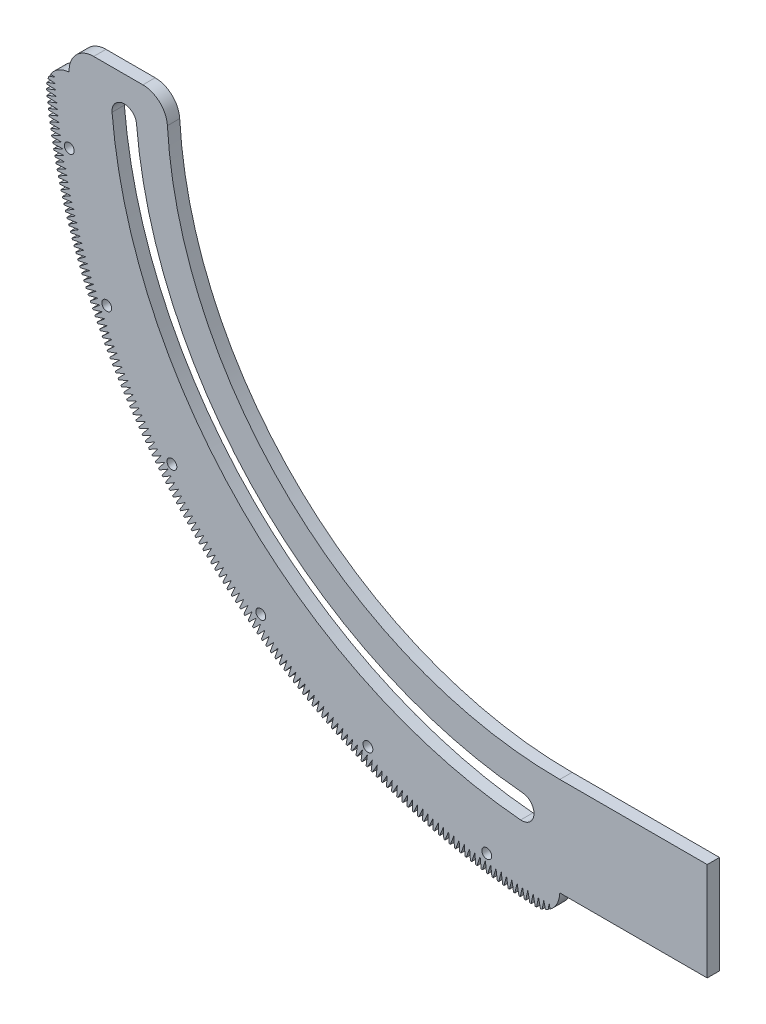
SolidWorks part; units mm, degrees
ref_plane "Front Plane" through (0, 0, 0) normal (0, 0, 1) x (1, 0, 0)
ref_plane "Top Plane" through (0, 0, 0) normal (0, 1, 0) x (1, 0, 0)
ref_plane "Right Plane" through (0, 0, 0) normal (1, 0, 0) x (0, 0, -1)
sketch "Sketch1" plane through (0, 0, 0) normal (0, 0, 1) x (1, 0, 0)
  line L0 (0, 0) -> (-203.2, 0) construction
  line L1 (0, 0) -> (0, -203.2) construction
  line L2 (0, -203.2) -> (76.2, -203.2)
  line L3 (0, -254) -> (76.2, -254)
  line L4 (-254, 0) -> (-203.2, 0)
  line L5 (76.2, -203.2) -> (76.2, -254)
  arc A0 (-203.2, 0) -> (0, -203.2) centre (0, 0) ccw
  arc A1 (-254, 0) -> (0, -254) centre (0, 0) ccw
  dimension "D1" = 50.8
  dimension "D2" = 76.2
  dimension "D3" = 203.2
extrude "Boss-Extrude1" add sketch "Sketch1" along normal blind 6.35
ref_plane "Mid_Plane" through (0, 0, 3.175) normal (0, 0, 1) x (1, 0, 0)
sketch "Sketch2" plane through (0, 0, 6.35) normal (0, 0, 1) x (1, 0, 0)
  line L0 (0, 0) -> (-229.3095, 0) construction
  line L1 (0, 0) -> (-225.1381, -19.697) construction
  line L2 (0, 0) -> (-19.697, -225.1381) construction
  arc A0 (-225.1381, -19.697) -> (-19.697, -225.1381) centre (0, 0) ccw construction
  arc A1 (-225.1381, -19.697) -> (-19.697, -225.1381) centre (0, 0) ccw construction
  arc A2 (-231.4639, -20.2505) -> (-20.2505, -231.4639) centre (0, 0) ccw
  arc A3 (-218.8123, -19.1436) -> (-19.1436, -218.8123) centre (0, 0) ccw
  arc A4 (-218.8123, -19.1436) -> (-231.4639, -20.2505) centre (-225.1381, -19.697) ccw
  arc A5 (-20.2505, -231.4639) -> (-19.1436, -218.8123) centre (-19.697, -225.1381) ccw
  point P5 (-159.8048, -159.8048)
  dimension "D1" = 80
  dimension "D3" = 12.7
  dimension "D2" = 5
extrude "Cut-Extrude1" cut sketch "Sketch2" against normal up to next
fillet "Fillet1" radius 12.7 2 edges at (-203.2, 0, 3.175) (-254, 0, 3.175)
ref_point "Mid_Point"
sketch "Sketch4" plane through (0, 0, 0) normal (0, 0, -1) x (-1, 0, 0)
  line L0 (253.648, -13.3684) -> (266.3304, -14.0368)
  line L1 (0, -254) -> (0, -266.7)
  arc A0 (0, -254) -> (253.648, -13.3684) centre (0, 0) ccw construction
  arc A1 (0, -254) -> (253.648, -13.3684) centre (0, 0) ccw
  arc A2 (0, -266.7) -> (266.3304, -14.0368) centre (0, 0) ccw
extrude "Boss-Extrude3" add sketch "Sketch4" against normal up to surface (6.35 mm away) up to face at (-139.6681, -139.6681, 6.35)
fillet "Fillet2" radius 12.7 2 edges at (-266.3304, -14.0368, 3.175) (0, -266.7, 3.175)
sketch "Sketch5" plane through (0, 0, 0) normal (0, 0, -1) x (-1, 0, 0)
  line L0 (2.758, -261.6055) -> (3.6103, -266.6756)
  line L1 (0, 0) -> (306.4939, -16.1536) construction
  line L2 (0, -261.62) -> (0.7987, -266.6988)
  line L3 (0, -261.62) -> (-1.3603, -266.6965)
  line L4 (2.758, -261.6055) -> (1.4514, -266.6961)
  line L5 (5.5157, -261.5618) -> (6.4214, -266.6227)
  line L6 (5.5157, -261.5618) -> (4.2628, -266.6659)
  line L7 (8.2728, -261.4892) -> (9.2318, -266.5402)
  line L8 (8.2728, -261.4892) -> (7.0738, -266.6062)
  line L9 (11.029, -261.3874) -> (12.0411, -266.428)
  line L10 (11.029, -261.3874) -> (9.884, -266.5168)
  line L11 (13.7839, -261.2566) -> (14.8492, -266.2863)
  line L12 (13.7839, -261.2566) -> (12.693, -266.3978)
  line L13 (16.5374, -261.0968) -> (17.6555, -266.115)
  line L14 (16.5374, -261.0968) -> (15.5007, -266.2492)
  line L15 (19.2889, -260.908) -> (20.46, -265.914)
  line L16 (19.2889, -260.908) -> (18.3067, -266.071)
  line L17 (22.0384, -260.6901) -> (23.2621, -265.6836)
  line L18 (22.0384, -260.6901) -> (21.1106, -265.8632)
  line L19 (24.7854, -260.4433) -> (26.0617, -265.4236)
  line L20 (24.7854, -260.4433) -> (23.9122, -265.6259)
  line L21 (27.5296, -260.1675) -> (28.8583, -265.1341)
  line L22 (27.5296, -260.1675) -> (26.7111, -265.359)
  line L23 (30.2708, -259.8629) -> (31.6518, -264.8151)
  line L24 (30.2708, -259.8629) -> (29.507, -265.0627)
  line L25 (33.0086, -259.5293) -> (34.4417, -264.4667)
  line L26 (33.0086, -259.5293) -> (32.2997, -264.7369)
  line L27 (35.7427, -259.1669) -> (37.2278, -264.089)
  line L28 (35.7427, -259.1669) -> (35.0888, -264.3817)
  line L29 (38.4729, -258.7757) -> (40.0098, -263.6818)
  line L30 (38.4729, -258.7757) -> (37.874, -263.9971)
  line L31 (41.1988, -258.3557) -> (42.7873, -263.2454)
  line L32 (41.1988, -258.3557) -> (40.6549, -263.5831)
  line L33 (43.9201, -257.9071) -> (45.5601, -262.7797)
  line L34 (43.9201, -257.9071) -> (43.4314, -263.1399)
  line L35 (46.6365, -257.4297) -> (48.3278, -262.2848)
  line L36 (46.6365, -257.4297) -> (46.203, -262.6674)
  line L37 (49.3478, -256.9238) -> (51.0902, -261.7607)
  line L38 (49.3478, -256.9238) -> (48.9695, -262.1657)
  line L39 (52.0535, -256.3893) -> (53.8468, -261.2076)
  line L40 (52.0535, -256.3893) -> (51.7305, -261.6349)
  line L41 (54.7535, -255.8263) -> (56.5975, -260.6254)
  line L42 (54.7535, -255.8263) -> (54.4858, -261.0751)
  line L43 (57.4474, -255.2348) -> (59.3419, -260.0143)
  line L44 (57.4474, -255.2348) -> (57.2351, -260.4862)
  line L45 (60.1349, -254.615) -> (62.0797, -259.3743)
  line L46 (60.1349, -254.615) -> (59.978, -259.8683)
  line L47 (62.8157, -253.9669) -> (64.8106, -258.7054)
  line L48 (62.8157, -253.9669) -> (62.7142, -259.2216)
  line L49 (65.4896, -253.2906) -> (67.5342, -258.0078)
  line L50 (65.4896, -253.2906) -> (65.4434, -258.546)
  line L51 (68.1561, -252.5862) -> (70.2504, -257.2815)
  line L52 (68.1561, -252.5862) -> (68.1654, -257.8418)
  line L53 (70.8151, -251.8536) -> (72.9588, -256.5266)
  line L54 (70.8151, -251.8536) -> (70.8798, -257.1088)
  line L55 (73.4663, -251.0931) -> (75.6591, -255.7432)
  line L56 (73.4663, -251.0931) -> (73.5863, -256.3473)
  line L57 (76.1092, -250.3046) -> (78.3509, -254.9314)
  line L58 (76.1092, -250.3046) -> (76.2846, -255.5573)
  line L59 (78.7437, -249.4884) -> (81.0341, -254.0913)
  line L60 (78.7437, -249.4884) -> (78.9745, -254.7389)
  line L61 (81.3695, -248.6444) -> (83.7082, -253.2229)
  line L62 (81.3695, -248.6444) -> (81.6556, -253.8922)
  line L63 (83.9862, -247.7728) -> (86.373, -252.3263)
  line L64 (83.9862, -247.7728) -> (84.3276, -253.0173)
  line L65 (86.5935, -246.8736) -> (89.0283, -251.4018)
  line L66 (86.5935, -246.8736) -> (86.9902, -252.1142)
  line L67 (89.1913, -245.947) -> (91.6736, -250.4493)
  line L68 (89.1913, -245.947) -> (89.6432, -251.1832)
  line L69 (91.7791, -244.9931) -> (94.3088, -249.4689)
  line L70 (91.7791, -244.9931) -> (92.2862, -250.2242)
  line L71 (94.3567, -244.0119) -> (96.9335, -248.4608)
  line L72 (94.3567, -244.0119) -> (94.919, -249.2374)
  line L73 (96.9239, -243.0037) -> (99.5474, -247.4252)
  line L74 (96.9239, -243.0037) -> (97.5412, -248.2229)
  line L75 (99.4803, -241.9684) -> (102.1502, -246.362)
  line L76 (99.4803, -241.9684) -> (100.1525, -247.1808)
  line L77 (102.0256, -240.9062) -> (104.7417, -245.2714)
  line L78 (102.0256, -240.9062) -> (102.7528, -246.1113)
  line L79 (104.5596, -239.8173) -> (107.3215, -244.1536)
  line L80 (104.5596, -239.8173) -> (105.3416, -245.0144)
  line L81 (107.0819, -238.7017) -> (109.8895, -243.0086)
  line L82 (107.0819, -238.7017) -> (107.9187, -243.8902)
  line L83 (109.5924, -237.5595) -> (112.4452, -241.8367)
  line L84 (109.5924, -237.5595) -> (110.4838, -242.739)
  line L85 (112.0907, -236.391) -> (114.9884, -240.6378)
  line L86 (112.0907, -236.391) -> (113.0366, -241.5608)
  line L87 (114.5765, -235.1962) -> (117.5188, -239.4122)
  line L88 (114.5765, -235.1962) -> (115.5769, -240.3557)
  line L89 (117.0496, -233.9753) -> (120.0362, -238.16)
  line L90 (117.0496, -233.9753) -> (118.1043, -239.124)
  line L91 (119.5096, -232.7283) -> (122.5402, -236.8814)
  line L92 (119.5096, -232.7283) -> (120.6186, -237.8656)
  line L93 (121.9564, -231.4555) -> (125.0306, -235.5764)
  line L94 (121.9564, -231.4555) -> (123.1195, -236.5808)
  line L95 (124.3897, -230.157) -> (127.5071, -234.2452)
  line L96 (124.3897, -230.157) -> (125.6067, -235.2697)
  line L97 (126.8091, -228.8329) -> (129.9695, -232.888)
  line L98 (126.8091, -228.8329) -> (128.0799, -233.9325)
  line L99 (129.2144, -227.4833) -> (132.4174, -231.5049)
  line L100 (129.2144, -227.4833) -> (130.539, -232.5693)
  line L101 (131.6054, -226.1085) -> (134.8505, -230.0961)
  line L102 (131.6054, -226.1085) -> (132.9835, -231.1802)
  line L103 (133.9817, -224.7085) -> (137.2687, -228.6617)
  line L104 (133.9817, -224.7085) -> (135.4132, -229.7654)
  line L105 (136.3432, -223.2836) -> (139.6717, -227.2019)
  line L106 (136.3432, -223.2836) -> (137.8279, -228.3251)
  line L107 (138.6895, -221.8339) -> (142.0591, -225.7169)
  line L108 (138.6895, -221.8339) -> (140.2272, -226.8595)
  line L109 (141.0203, -220.3595) -> (144.4307, -224.2067)
  line L110 (141.0203, -220.3595) -> (142.611, -225.3686)
  line L111 (143.3355, -218.8606) -> (146.7863, -222.6717)
  line L112 (143.3355, -218.8606) -> (144.9789, -223.8526)
  line L113 (145.6348, -217.3374) -> (149.1256, -221.1119)
  line L114 (145.6348, -217.3374) -> (147.3307, -222.3118)
  line L115 (147.9179, -215.79) -> (151.4482, -219.5275)
  line L116 (147.9179, -215.79) -> (149.6662, -220.7463)
  line L117 (150.1846, -214.2186) -> (153.7541, -217.9187)
  line L118 (150.1846, -214.2186) -> (151.985, -219.1562)
  line L119 (152.4345, -212.6235) -> (156.0429, -216.2857)
  line L120 (152.4345, -212.6235) -> (154.2869, -217.5418)
  line L121 (154.6675, -211.0047) -> (158.3143, -214.6287)
  line L122 (154.6675, -211.0047) -> (156.5717, -215.9032)
  line L123 (156.8834, -209.3624) -> (160.5681, -212.9478)
  line L124 (156.8834, -209.3624) -> (158.839, -214.2407)
  line L125 (159.0818, -207.6969) -> (162.8041, -211.2432)
  line L126 (159.0818, -207.6969) -> (161.0887, -212.5543)
  line L127 (161.2625, -206.0083) -> (165.022, -209.5152)
  line L128 (161.2625, -206.0083) -> (163.3205, -210.8442)
  line L129 (163.4253, -204.2969) -> (167.2216, -207.7639)
  line L130 (163.4253, -204.2969) -> (165.5342, -209.1108)
  line L131 (165.5699, -202.5627) -> (169.4025, -205.9895)
  line L132 (165.5699, -202.5627) -> (167.7295, -207.3541)
  line L133 (167.6961, -200.806) -> (171.5647, -204.1922)
  line L134 (167.6961, -200.806) -> (169.9061, -205.5744)
  line L135 (169.8037, -199.0269) -> (173.7077, -202.3722)
  line L136 (169.8037, -199.0269) -> (172.0638, -203.7718)
  line L137 (171.8924, -197.2258) -> (175.8315, -200.5297)
  line L138 (171.8924, -197.2258) -> (174.2024, -201.9465)
  line L139 (173.962, -195.4027) -> (177.9357, -198.665)
  line L140 (173.962, -195.4027) -> (176.3217, -200.0989)
  line L141 (176.0123, -193.558) -> (180.0202, -196.7781)
  line L142 (176.0123, -193.558) -> (178.4213, -198.229)
  line L143 (178.043, -191.6917) -> (182.0846, -194.8694)
  line L144 (178.043, -191.6917) -> (180.5012, -196.337)
  line L145 (180.054, -189.8041) -> (184.1288, -192.939)
  line L146 (180.054, -189.8041) -> (182.5609, -194.4232)
  line L147 (182.0449, -187.8954) -> (186.1526, -190.9872)
  line L148 (182.0449, -187.8954) -> (184.6004, -192.4879)
  line L149 (184.0156, -185.9658) -> (188.1556, -189.0141)
  line L150 (184.0156, -185.9658) -> (186.6194, -190.5311)
  line L151 (185.9658, -184.0156) -> (190.1378, -187.0201)
  line L152 (185.9658, -184.0156) -> (188.6176, -188.5532)
  line L153 (187.8954, -182.0449) -> (192.0988, -185.0053)
  line L154 (187.8954, -182.0449) -> (190.5948, -186.5543)
  line L155 (189.8041, -180.054) -> (194.0384, -182.9699)
  line L156 (189.8041, -180.054) -> (192.5509, -184.5346)
  line L157 (191.6917, -178.043) -> (195.9565, -180.9141)
  line L158 (191.6917, -178.043) -> (194.4856, -182.4945)
  line L159 (193.558, -176.0123) -> (197.8529, -178.8383)
  line L160 (193.558, -176.0123) -> (196.3987, -180.4341)
  line L161 (195.4027, -173.962) -> (199.7272, -176.7426)
  line L162 (195.4027, -173.962) -> (198.2899, -178.3536)
  line L163 (197.2258, -171.8924) -> (201.5793, -174.6272)
  line L164 (197.2258, -171.8924) -> (200.1591, -176.2533)
  line L165 (199.0269, -169.8037) -> (203.4091, -172.4925)
  line L166 (199.0269, -169.8037) -> (202.006, -174.1334)
  line L167 (200.806, -167.6961) -> (205.2162, -170.3385)
  line L168 (200.806, -167.6961) -> (203.8305, -171.9942)
  line L169 (202.5627, -165.5699) -> (207.0005, -168.1656)
  line L170 (202.5627, -165.5699) -> (205.6324, -169.8358)
  line L171 (204.2969, -163.4253) -> (208.7618, -165.9741)
  line L172 (204.2969, -163.4253) -> (207.4114, -167.6586)
  line L173 (206.0083, -161.2625) -> (210.4999, -163.7641)
  line L174 (206.0083, -161.2625) -> (209.1673, -165.4628)
  line L175 (207.6969, -159.0818) -> (212.2146, -161.5359)
  line L176 (207.6969, -159.0818) -> (210.9, -163.2485)
  line L177 (209.3624, -156.8834) -> (213.9058, -159.2897)
  line L178 (209.3624, -156.8834) -> (212.6093, -161.0161)
  line L179 (211.0047, -154.6675) -> (215.5731, -157.0259)
  line L180 (211.0047, -154.6675) -> (214.2949, -158.7658)
  line L181 (212.6235, -152.4345) -> (217.2165, -154.7446)
  line L182 (212.6235, -152.4345) -> (215.9567, -156.4979)
  line L183 (214.2186, -150.1846) -> (218.8358, -152.446)
  line L184 (214.2186, -150.1846) -> (217.5945, -154.2126)
  line L185 (215.79, -147.9179) -> (220.4307, -150.1306)
  line L186 (215.79, -147.9179) -> (219.2081, -151.9101)
  line L187 (217.3374, -145.6348) -> (222.0011, -147.7985)
  line L188 (217.3374, -145.6348) -> (220.7974, -149.5908)
  line L189 (218.8606, -143.3355) -> (223.5469, -145.4499)
  line L190 (218.8606, -143.3355) -> (222.3621, -147.2548)
  line L191 (220.3595, -141.0203) -> (225.0678, -143.0852)
  line L192 (220.3595, -141.0203) -> (223.9021, -144.9024)
  line L193 (221.8339, -138.6895) -> (226.5637, -140.7045)
  line L194 (221.8339, -138.6895) -> (225.4173, -142.534)
  line L195 (223.2836, -136.3432) -> (228.0345, -138.3083)
  line L196 (223.2836, -136.3432) -> (226.9074, -140.1497)
  line L197 (224.7085, -133.9817) -> (229.4798, -135.8966)
  line L198 (224.7085, -133.9817) -> (228.3722, -137.7499)
  line L199 (226.1085, -131.6054) -> (230.8997, -133.4699)
  line L200 (226.1085, -131.6054) -> (229.8117, -135.3347)
  line L201 (227.4833, -129.2144) -> (232.2939, -131.0283)
  line L202 (227.4833, -129.2144) -> (231.2256, -132.9045)
  line L203 (228.8329, -126.8091) -> (233.6623, -128.5722)
  line L204 (228.8329, -126.8091) -> (232.6139, -130.4595)
  line L205 (230.157, -124.3897) -> (235.0048, -126.1017)
  line L206 (230.157, -124.3897) -> (233.9762, -128)
  line L207 (231.4555, -121.9564) -> (236.3211, -123.6173)
  line L208 (231.4555, -121.9564) -> (235.3126, -125.5263)
  line L209 (232.7283, -119.5096) -> (237.6111, -121.1191)
  line L210 (232.7283, -119.5096) -> (236.6229, -123.0387)
  line L211 (233.9753, -117.0496) -> (238.8748, -118.6075)
  line L212 (233.9753, -117.0496) -> (237.9068, -120.5373)
  line L213 (235.1962, -114.5765) -> (240.1119, -116.0827)
  line L214 (235.1962, -114.5765) -> (239.1643, -118.0226)
  line L215 (236.391, -112.0907) -> (241.3223, -113.5449)
  line L216 (236.391, -112.0907) -> (240.3952, -115.4948)
  line L217 (237.5595, -109.5924) -> (242.5059, -110.9946)
  line L218 (237.5595, -109.5924) -> (241.5994, -112.9541)
  line L219 (238.7017, -107.0819) -> (243.6625, -108.4319)
  line L220 (238.7017, -107.0819) -> (242.7767, -110.4009)
  line L221 (239.8173, -104.5596) -> (244.792, -105.8572)
  line L222 (239.8173, -104.5596) -> (243.9271, -107.8353)
  line L223 (240.9062, -102.0256) -> (245.8944, -103.2707)
  line L224 (240.9062, -102.0256) -> (245.0503, -105.2579)
  line L225 (241.9684, -99.4803) -> (246.9694, -100.6727)
  line L226 (241.9684, -99.4803) -> (246.1464, -102.6687)
  line L227 (243.0037, -96.9239) -> (248.017, -98.0636)
  line L228 (243.0037, -96.9239) -> (247.215, -100.0681)
  line L229 (244.0119, -94.3567) -> (249.037, -95.4435)
  line L230 (244.0119, -94.3567) -> (248.2562, -97.4564)
  line L231 (244.9931, -91.7791) -> (250.0293, -92.8128)
  line L232 (244.9931, -91.7791) -> (249.2698, -94.8338)
  line L233 (245.947, -89.1913) -> (250.9939, -90.1718)
  line L234 (245.947, -89.1913) -> (250.2557, -92.2007)
  line L235 (246.8736, -86.5935) -> (251.9305, -87.5208)
  line L236 (246.8736, -86.5935) -> (251.2138, -89.5574)
  line L237 (247.7728, -83.9862) -> (252.8392, -84.8601)
  line L238 (247.7728, -83.9862) -> (252.1439, -86.9041)
  line L239 (248.6444, -81.3695) -> (253.7197, -82.1899)
  line L240 (248.6444, -81.3695) -> (253.0461, -84.2412)
  line L241 (249.4884, -78.7437) -> (254.5721, -79.5107)
  line L242 (249.4884, -78.7437) -> (253.9201, -81.5689)
  line L243 (250.3046, -76.1092) -> (255.3961, -76.8225)
  line L244 (250.3046, -76.1092) -> (254.7659, -78.8875)
  line L245 (251.0931, -73.4663) -> (256.1918, -74.1258)
  line L246 (251.0931, -73.4663) -> (255.5834, -76.1973)
  line L247 (251.8536, -70.8151) -> (256.959, -71.4209)
  line L248 (251.8536, -70.8151) -> (256.3724, -73.4987)
  line L249 (252.5862, -68.1561) -> (257.6977, -68.7081)
  line L250 (252.5862, -68.1561) -> (257.133, -70.7919)
  line L251 (253.2906, -65.4896) -> (258.4077, -65.9876)
  line L252 (253.2906, -65.4896) -> (257.865, -68.0773)
  line L253 (253.9669, -62.8157) -> (259.089, -63.2598)
  line L254 (253.9669, -62.8157) -> (258.5684, -65.3551)
  line L255 (254.615, -60.1349) -> (259.7415, -60.5249)
  line L256 (254.615, -60.1349) -> (259.243, -62.6256)
  line L257 (255.2348, -57.4474) -> (260.3651, -57.7834)
  line L258 (255.2348, -57.4474) -> (259.8888, -59.8892)
  line L259 (255.8263, -54.7535) -> (260.9598, -55.0354)
  line L260 (255.8263, -54.7535) -> (260.5057, -57.1461)
  line L261 (256.3893, -52.0535) -> (261.5254, -52.2813)
  line L262 (256.3893, -52.0535) -> (261.0937, -54.3966)
  line L263 (256.9238, -49.3478) -> (262.0621, -49.5213)
  line L264 (256.9238, -49.3478) -> (261.6526, -51.6412)
  line L265 (257.4297, -46.6365) -> (262.5696, -46.7559)
  line L266 (257.4297, -46.6365) -> (262.1825, -48.8799)
  line L267 (257.9071, -43.9201) -> (263.0479, -43.9853)
  line L268 (257.9071, -43.9201) -> (262.6832, -46.1133)
  line L269 (258.3557, -41.1988) -> (263.497, -41.2098)
  line L270 (258.3557, -41.1988) -> (263.1547, -43.3415)
  line L271 (258.7757, -38.4729) -> (263.9167, -38.4297)
  line L272 (258.7757, -38.4729) -> (263.597, -40.5649)
  line L273 (259.1669, -35.7427) -> (264.3072, -35.6453)
  line L274 (259.1669, -35.7427) -> (264.01, -37.7838)
  line L275 (259.5293, -33.0086) -> (264.6683, -32.857)
  line L276 (259.5293, -33.0086) -> (264.3936, -34.9985)
  line L277 (259.8629, -30.2708) -> (265, -30.065)
  line L278 (259.8629, -30.2708) -> (264.7479, -32.2093)
  line L279 (260.1675, -27.5296) -> (265.3022, -27.2697)
  line L280 (260.1675, -27.5296) -> (265.0727, -29.4165)
  line L281 (260.4433, -24.7854) -> (265.5749, -24.4714)
  line L282 (260.4433, -24.7854) -> (265.3681, -26.6204)
  line L283 (260.6901, -22.0384) -> (265.8181, -21.6703)
  line L284 (260.6901, -22.0384) -> (265.634, -23.8214)
  line L285 (260.908, -19.2889) -> (266.0318, -18.8668)
  line L286 (260.908, -19.2889) -> (265.8704, -21.0198)
  line L287 (261.0968, -16.5374) -> (266.2159, -16.0612)
  line L288 (261.0968, -16.5374) -> (266.0772, -18.2158)
  line L289 (261.2566, -13.7839) -> (266.3705, -13.2539)
  line L290 (261.2566, -13.7839) -> (266.2544, -15.4098)
  line L291 (261.3874, -11.029) -> (266.4954, -10.4451)
  line L292 (261.3874, -11.029) -> (266.4021, -12.602)
  line L301 (0, 0) -> (0, -261.62) construction
  arc A0 (13.3308, -266.3666) -> (265.2958, -27.3317) centre (0, 0) ccw construction
  arc A1 (-1.3603, -266.6965) -> (0.7987, -266.6988) centre (0, 0) ccw
  arc A2 (1.4514, -266.6961) -> (3.6103, -266.6756) centre (0, 0) ccw
  arc A3 (4.2628, -266.6659) -> (6.4214, -266.6227) centre (0, 0) ccw
  arc A4 (7.0738, -266.6062) -> (9.2318, -266.5402) centre (0, 0) ccw
  arc A5 (9.884, -266.5168) -> (12.0411, -266.428) centre (0, 0) ccw
  arc A6 (12.693, -266.3978) -> (14.8492, -266.2863) centre (0, 0) ccw
  arc A7 (15.5007, -266.2492) -> (17.6555, -266.115) centre (0, 0) ccw
  arc A8 (18.3067, -266.071) -> (20.46, -265.914) centre (0, 0) ccw
  arc A9 (21.1106, -265.8632) -> (23.2621, -265.6836) centre (0, 0) ccw
  arc A10 (23.9122, -265.6259) -> (26.0617, -265.4236) centre (0, 0) ccw
  arc A11 (26.7111, -265.359) -> (28.8583, -265.1341) centre (0, 0) ccw
  arc A12 (29.507, -265.0627) -> (31.6518, -264.8151) centre (0, 0) ccw
  arc A13 (32.2997, -264.7369) -> (34.4417, -264.4667) centre (0, 0) ccw
  arc A14 (35.0888, -264.3817) -> (37.2278, -264.089) centre (0, 0) ccw
  arc A15 (37.874, -263.9971) -> (40.0098, -263.6818) centre (0, 0) ccw
  arc A16 (40.6549, -263.5831) -> (42.7873, -263.2454) centre (0, 0) ccw
  arc A17 (43.4314, -263.1399) -> (45.5601, -262.7797) centre (0, 0) ccw
  arc A18 (46.203, -262.6674) -> (48.3278, -262.2848) centre (0, 0) ccw
  arc A19 (48.9695, -262.1657) -> (51.0902, -261.7607) centre (0, 0) ccw
  arc A20 (51.7305, -261.6349) -> (53.8468, -261.2076) centre (0, 0) ccw
  arc A21 (54.4858, -261.0751) -> (56.5975, -260.6254) centre (0, 0) ccw
  arc A22 (57.2351, -260.4862) -> (59.3419, -260.0143) centre (0, 0) ccw
  arc A23 (59.978, -259.8683) -> (62.0797, -259.3743) centre (0, 0) ccw
  arc A24 (62.7142, -259.2216) -> (64.8106, -258.7054) centre (0, 0) ccw
  arc A25 (65.4434, -258.546) -> (67.5342, -258.0078) centre (0, 0) ccw
  arc A26 (68.1654, -257.8418) -> (70.2504, -257.2815) centre (0, 0) ccw
  arc A27 (70.8798, -257.1088) -> (72.9588, -256.5266) centre (0, 0) ccw
  arc A28 (73.5863, -256.3473) -> (75.6591, -255.7432) centre (0, 0) ccw
  arc A29 (76.2846, -255.5573) -> (78.3509, -254.9314) centre (0, 0) ccw
  arc A30 (78.9745, -254.7389) -> (81.0341, -254.0913) centre (0, 0) ccw
  arc A31 (81.6556, -253.8922) -> (83.7082, -253.2229) centre (0, 0) ccw
  arc A32 (84.3276, -253.0173) -> (86.373, -252.3263) centre (0, 0) ccw
  arc A33 (86.9902, -252.1142) -> (89.0283, -251.4018) centre (0, 0) ccw
  arc A34 (89.6432, -251.1832) -> (91.6736, -250.4493) centre (0, 0) ccw
  arc A35 (92.2862, -250.2242) -> (94.3088, -249.4689) centre (0, 0) ccw
  arc A36 (94.919, -249.2374) -> (96.9335, -248.4608) centre (0, 0) ccw
  arc A37 (97.5412, -248.2229) -> (99.5474, -247.4252) centre (0, 0) ccw
  arc A38 (100.1525, -247.1808) -> (102.1502, -246.362) centre (0, 0) ccw
  arc A39 (102.7528, -246.1113) -> (104.7417, -245.2714) centre (0, 0) ccw
  arc A40 (105.3416, -245.0144) -> (107.3215, -244.1536) centre (0, 0) ccw
  arc A41 (107.9187, -243.8902) -> (109.8895, -243.0086) centre (0, 0) ccw
  arc A42 (110.4838, -242.739) -> (112.4452, -241.8367) centre (0, 0) ccw
  arc A43 (113.0366, -241.5608) -> (114.9884, -240.6378) centre (0, 0) ccw
  arc A44 (115.5769, -240.3557) -> (117.5188, -239.4122) centre (0, 0) ccw
  arc A45 (118.1043, -239.124) -> (120.0362, -238.16) centre (0, 0) ccw
  arc A46 (120.6186, -237.8656) -> (122.5402, -236.8814) centre (0, 0) ccw
  arc A47 (123.1195, -236.5808) -> (125.0306, -235.5764) centre (0, 0) ccw
  arc A48 (125.6067, -235.2697) -> (127.5071, -234.2452) centre (0, 0) ccw
  arc A49 (128.0799, -233.9325) -> (129.9695, -232.888) centre (0, 0) ccw
  arc A50 (130.539, -232.5693) -> (132.4174, -231.5049) centre (0, 0) ccw
  arc A51 (132.9835, -231.1802) -> (134.8505, -230.0961) centre (0, 0) ccw
  arc A52 (135.4132, -229.7654) -> (137.2687, -228.6617) centre (0, 0) ccw
  arc A53 (137.8279, -228.3251) -> (139.6717, -227.2019) centre (0, 0) ccw
  arc A54 (140.2272, -226.8595) -> (142.0591, -225.7169) centre (0, 0) ccw
  arc A55 (142.611, -225.3686) -> (144.4307, -224.2067) centre (0, 0) ccw
  arc A56 (144.9789, -223.8526) -> (146.7863, -222.6717) centre (0, 0) ccw
  arc A57 (147.3307, -222.3118) -> (149.1256, -221.1119) centre (0, 0) ccw
  arc A58 (149.6662, -220.7463) -> (151.4482, -219.5275) centre (0, 0) ccw
  arc A59 (151.985, -219.1562) -> (153.7541, -217.9187) centre (0, 0) ccw
  arc A60 (154.2869, -217.5418) -> (156.0429, -216.2857) centre (0, 0) ccw
  arc A61 (156.5717, -215.9032) -> (158.3143, -214.6287) centre (0, 0) ccw
  arc A62 (158.839, -214.2407) -> (160.5681, -212.9478) centre (0, 0) ccw
  arc A63 (161.0887, -212.5543) -> (162.8041, -211.2432) centre (0, 0) ccw
  arc A64 (163.3205, -210.8442) -> (165.022, -209.5152) centre (0, 0) ccw
  arc A65 (165.5342, -209.1108) -> (167.2216, -207.7639) centre (0, 0) ccw
  arc A66 (167.7295, -207.3541) -> (169.4025, -205.9895) centre (0, 0) ccw
  arc A67 (169.9061, -205.5744) -> (171.5647, -204.1922) centre (0, 0) ccw
  arc A68 (172.0638, -203.7718) -> (173.7077, -202.3722) centre (0, 0) ccw
  arc A69 (174.2024, -201.9465) -> (175.8315, -200.5297) centre (0, 0) ccw
  arc A70 (176.3217, -200.0989) -> (177.9357, -198.665) centre (0, 0) ccw
  arc A71 (178.4213, -198.229) -> (180.0202, -196.7781) centre (0, 0) ccw
  arc A72 (180.5012, -196.337) -> (182.0846, -194.8694) centre (0, 0) ccw
  arc A73 (182.5609, -194.4232) -> (184.1288, -192.939) centre (0, 0) ccw
  arc A74 (184.6004, -192.4879) -> (186.1526, -190.9872) centre (0, 0) ccw
  arc A75 (186.6194, -190.5311) -> (188.1556, -189.0141) centre (0, 0) ccw
  arc A76 (188.6176, -188.5532) -> (190.1378, -187.0201) centre (0, 0) ccw
  arc A77 (190.5948, -186.5543) -> (192.0988, -185.0053) centre (0, 0) ccw
  arc A78 (192.5509, -184.5346) -> (194.0384, -182.9699) centre (0, 0) ccw
  arc A79 (194.4856, -182.4945) -> (195.9565, -180.9141) centre (0, 0) ccw
  arc A80 (196.3987, -180.4341) -> (197.8529, -178.8383) centre (0, 0) ccw
  arc A81 (198.2899, -178.3536) -> (199.7272, -176.7426) centre (0, 0) ccw
  arc A82 (200.1591, -176.2533) -> (201.5793, -174.6272) centre (0, 0) ccw
  arc A83 (202.006, -174.1334) -> (203.4091, -172.4925) centre (0, 0) ccw
  arc A84 (203.8305, -171.9942) -> (205.2162, -170.3385) centre (0, 0) ccw
  arc A85 (205.6324, -169.8358) -> (207.0005, -168.1656) centre (0, 0) ccw
  arc A86 (207.4114, -167.6586) -> (208.7618, -165.9741) centre (0, 0) ccw
  arc A87 (209.1673, -165.4628) -> (210.4999, -163.7641) centre (0, 0) ccw
  arc A88 (210.9, -163.2485) -> (212.2146, -161.5359) centre (0, 0) ccw
  arc A89 (212.6093, -161.0161) -> (213.9058, -159.2897) centre (0, 0) ccw
  arc A90 (214.2949, -158.7658) -> (215.5731, -157.0259) centre (0, 0) ccw
  arc A91 (215.9567, -156.4979) -> (217.2165, -154.7446) centre (0, 0) ccw
  arc A92 (217.5945, -154.2126) -> (218.8358, -152.446) centre (0, 0) ccw
  arc A93 (219.2081, -151.9101) -> (220.4307, -150.1306) centre (0, 0) ccw
  arc A94 (220.7974, -149.5908) -> (222.0011, -147.7985) centre (0, 0) ccw
  arc A95 (222.3621, -147.2548) -> (223.5469, -145.4499) centre (0, 0) ccw
  arc A96 (223.9021, -144.9024) -> (225.0678, -143.0852) centre (0, 0) ccw
  arc A97 (225.4173, -142.534) -> (226.5637, -140.7045) centre (0, 0) ccw
  arc A98 (226.9074, -140.1497) -> (228.0345, -138.3083) centre (0, 0) ccw
  arc A99 (228.3722, -137.7499) -> (229.4798, -135.8966) centre (0, 0) ccw
  arc A100 (229.8117, -135.3347) -> (230.8997, -133.4699) centre (0, 0) ccw
  arc A101 (231.2256, -132.9045) -> (232.2939, -131.0283) centre (0, 0) ccw
  arc A102 (232.6139, -130.4595) -> (233.6623, -128.5722) centre (0, 0) ccw
  arc A103 (233.9762, -128) -> (235.0048, -126.1017) centre (0, 0) ccw
  arc A104 (235.3126, -125.5263) -> (236.3211, -123.6173) centre (0, 0) ccw
  arc A105 (236.6229, -123.0387) -> (237.6111, -121.1191) centre (0, 0) ccw
  arc A106 (237.9068, -120.5373) -> (238.8748, -118.6075) centre (0, 0) ccw
  arc A107 (239.1643, -118.0226) -> (240.1119, -116.0827) centre (0, 0) ccw
  arc A108 (240.3952, -115.4948) -> (241.3223, -113.5449) centre (0, 0) ccw
  arc A109 (241.5994, -112.9541) -> (242.5059, -110.9946) centre (0, 0) ccw
  arc A110 (242.7767, -110.4009) -> (243.6625, -108.4319) centre (0, 0) ccw
  arc A111 (243.9271, -107.8353) -> (244.792, -105.8572) centre (0, 0) ccw
  arc A112 (245.0503, -105.2579) -> (245.8944, -103.2707) centre (0, 0) ccw
  arc A113 (246.1464, -102.6687) -> (246.9694, -100.6727) centre (0, 0) ccw
  arc A114 (247.215, -100.0681) -> (248.017, -98.0636) centre (0, 0) ccw
  arc A115 (248.2562, -97.4564) -> (249.037, -95.4435) centre (0, 0) ccw
  arc A116 (249.2698, -94.8338) -> (250.0293, -92.8128) centre (0, 0) ccw
  arc A117 (250.2557, -92.2007) -> (250.9939, -90.1718) centre (0, 0) ccw
  arc A118 (251.2138, -89.5574) -> (251.9305, -87.5208) centre (0, 0) ccw
  arc A119 (252.1439, -86.9041) -> (252.8392, -84.8601) centre (0, 0) ccw
  arc A120 (253.0461, -84.2412) -> (253.7197, -82.1899) centre (0, 0) ccw
  arc A121 (253.9201, -81.5689) -> (254.5721, -79.5107) centre (0, 0) ccw
  arc A122 (254.7659, -78.8875) -> (255.3961, -76.8225) centre (0, 0) ccw
  arc A123 (255.5834, -76.1973) -> (256.1918, -74.1258) centre (0, 0) ccw
  arc A124 (256.3724, -73.4987) -> (256.959, -71.4209) centre (0, 0) ccw
  arc A125 (257.133, -70.7919) -> (257.6977, -68.7081) centre (0, 0) ccw
  arc A126 (257.865, -68.0773) -> (258.4077, -65.9876) centre (0, 0) ccw
  arc A127 (258.5684, -65.3551) -> (259.089, -63.2598) centre (0, 0) ccw
  arc A128 (259.243, -62.6256) -> (259.7415, -60.5249) centre (0, 0) ccw
  arc A129 (259.8888, -59.8892) -> (260.3651, -57.7834) centre (0, 0) ccw
  arc A130 (260.5057, -57.1461) -> (260.9598, -55.0354) centre (0, 0) ccw
  arc A131 (261.0937, -54.3966) -> (261.5254, -52.2813) centre (0, 0) ccw
  arc A132 (261.6526, -51.6412) -> (262.0621, -49.5213) centre (0, 0) ccw
  arc A133 (262.1825, -48.8799) -> (262.5696, -46.7559) centre (0, 0) ccw
  arc A134 (262.6832, -46.1133) -> (263.0479, -43.9853) centre (0, 0) ccw
  arc A135 (263.1547, -43.3415) -> (263.497, -41.2098) centre (0, 0) ccw
  arc A136 (263.597, -40.5649) -> (263.9167, -38.4297) centre (0, 0) ccw
  arc A137 (264.01, -37.7838) -> (264.3072, -35.6453) centre (0, 0) ccw
  arc A138 (264.3936, -34.9985) -> (264.6683, -32.857) centre (0, 0) ccw
  arc A139 (264.7479, -32.2093) -> (265, -30.065) centre (0, 0) ccw
  arc A140 (265.0727, -29.4165) -> (265.3022, -27.2697) centre (0, 0) ccw
  arc A141 (265.3681, -26.6204) -> (265.5749, -24.4714) centre (0, 0) ccw
  arc A142 (265.634, -23.8214) -> (265.8181, -21.6703) centre (0, 0) ccw
  arc A143 (265.8704, -21.0198) -> (266.0318, -18.8668) centre (0, 0) ccw
  arc A144 (266.0772, -18.2158) -> (266.2159, -16.0612) centre (0, 0) ccw
  arc A145 (266.2544, -15.4098) -> (266.3705, -13.2539) centre (0, 0) ccw
  arc A146 (266.4021, -12.602) -> (266.4954, -10.4451) centre (0, 0) ccw
  dimension "D1" = 2.159
  dimension "D2" = 146
  dimension "D4" = 261.62
extrude "Cut-Extrude2" cut sketch "Sketch5" against normal up to surface (6.35 mm away) up to face at (-139.6681, -139.6681, 6.35)
sketch "Sketch6" plane through (0, 0, 6.35) normal (0, 0, 1) x (1, 0, 0)
  circle A1 centre (-253.5783, -47.3911) radius 2.54
  circle A2 centre (-234.2049, -108.1477) radius 2.54
  circle A3 centre (-200.5194, -162.2955) radius 2.54
  circle A4 centre (-154.5804, -206.5255) radius 2.54
  circle A5 centre (-99.195, -238.1349) radius 2.54
  circle A6 centre (-37.7479, -255.192) radius 2.54
  point P15 (0, 0)
  dimension "D1" = 6
extrude "Cut-Extrude3" cut sketch "Sketch6" against normal through all
